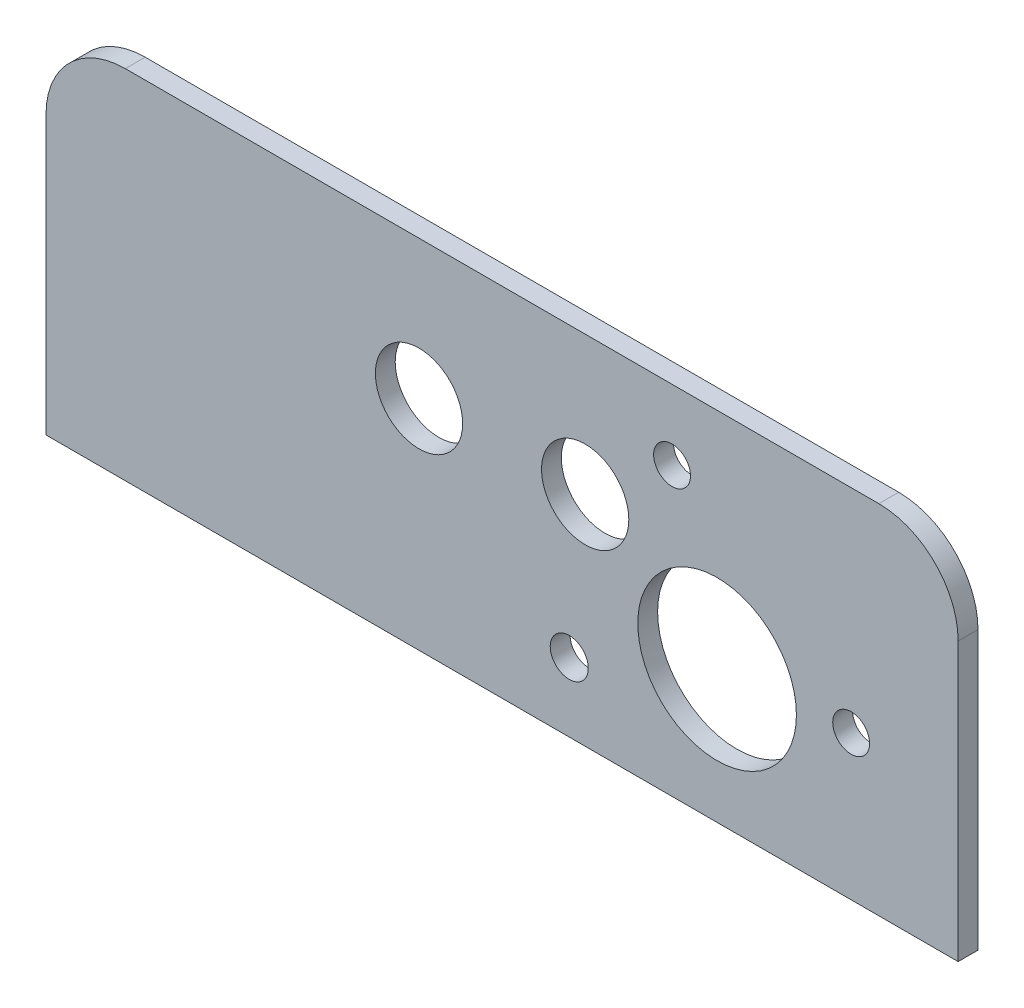
SolidWorks part; units mm, degrees
ref_plane "Front Plane" through (0, 0, 0) normal (0, 0, 1) x (1, 0, 0)
ref_plane "Top Plane" through (0, 0, 0) normal (0, 1, 0) x (1, 0, 0)
ref_plane "Right Plane" through (0, 0, 0) normal (1, 0, 0) x (0, 0, -1)
sketch "Sketch1" plane through (0, 0, 0) normal (0, 0, 1) x (1, 0, 0)
  line L1 (-115, -45) -> (115, -45)
  line L2 (-115, -45) -> (-115, 45)
  line L3 (-115, 45) -> (115, 45)
  line L4 (115, -45) -> (115, 45)
  line L5 (-115, -45) -> (115, 45) construction
  line L6 (-115, 45) -> (115, -45) construction
  point P0 (0, 0)
  dimension "D1" = 230
  dimension "D2" = 90
extrude "Boss-Extrude1" add sketch "Sketch1" along normal blind 5
fillet "Fillet1" radius 20 2 edges at (115, 45, 2.5) (-115, 45, 2.5)
sketch "Sketch2" plane through (0, 0, 5) normal (0, 0, 1) x (1, 0, 0)
  line L0 (-115, 10) -> (115, 10) construction
  line L1 (-115, 25) -> (-115, -45) construction
  line L2 (115, -45) -> (115, 25) construction
  circle A0 centre (-20.95, 10) radius 11
  circle A1 centre (20.95, 10) radius 11
  dimension "D2" = 22
  dimension "D1" = 41.9
  dimension "D3" = 20.95
  dimension "D7" = 10
extrude "Cut-Extrude1" cut sketch "Sketch2" against normal up to next
sketch "Sketch3" plane through (0, 0, 0) normal (0, 0, -1) x (-1, 0, 0)
  circle A0 centre (-42.8615, 27.3153) radius 4.65
  circle A1 centre (-88.0159, -8.5603) radius 4.65
  circle A2 centre (-16.9352, -27.6044) radius 4.8
extrude "Cut-Extrude2" cut sketch "Sketch3" against normal up to next
sketch "Sketch5" plane through (0, 0, 5) normal (0, 0, 1) x (1, 0, 0)
  circle A0 centre (54.2136, -11.5176) radius 20
  dimension "D1" = 40
extrude "Cut-Extrude3" cut sketch "Sketch5" against normal up to next
